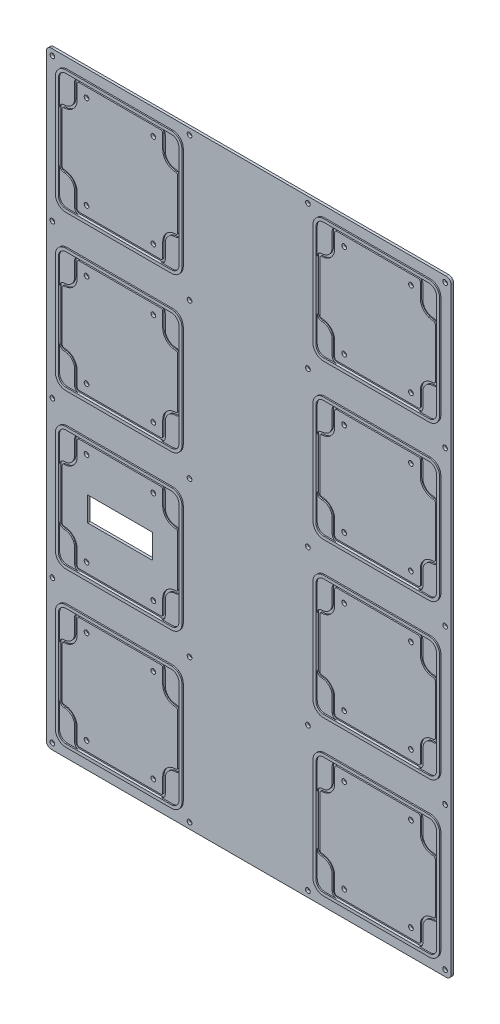
SolidWorks part; units mm, degrees
ref_plane "Front Plane" through (0, 0, 0) normal (0, 0, 1) x (1, 0, 0)
ref_plane "Top Plane" through (0, 0, 0) normal (0, 1, 0) x (1, 0, 0)
ref_plane "Right Plane" through (0, 0, 0) normal (1, 0, 0) x (0, 0, -1)
sketch "Sketch1" plane through (0, 0, 0) normal (0, 0, 1) x (1, 0, 0)
  line L1 (0, 0) -> (254, 0)
  line L2 (0, 0) -> (0, 381)
  line L3 (0, 381) -> (254, 381)
  line L4 (254, 0) -> (254, 381)
  dimension "D1" = 381
  dimension "D2" = 254
extrude "Boss-Extrude1" add sketch "Sketch1" along normal blind 1.5875
sketch "Sketch2" plane through (0, 0, 1.5875) normal (0, 0, 1) x (1, 0, 0)
  line L0 (89.8652, 377.19) -> (89.8652, 3.81) construction
  line L1 (0, 381) -> (254, 381) construction
  line L2 (127, 381) -> (127, 377.19) construction
  line L3 (3.81, 377.19) -> (250.19, 377.19) construction
  line L5 (164.1348, 377.19) -> (164.1348, 3.81) construction
  line L6 (3.81, 377.19) -> (3.81, 3.81) construction
  line L7 (3.81, 3.81) -> (250.19, 3.81) construction
  line L8 (250.19, 3.81) -> (250.19, 377.19) construction
  line L9 (3.81, 190.5) -> (250.19, 190.5) construction
  line L10 (3.81, 287.3756) -> (250.19, 287.3756) construction
  line L11 (3.81, 93.6244) -> (250.19, 93.6244) construction
  line L12 (0, 381) -> (0, 0) construction
  line L13 (0, 190.5) -> (3.81, 190.5) construction
  circle A0 centre (3.81, 377.19) radius 1.4732
  circle A1 centre (89.8652, 377.19) radius 1.4732
  circle A2 centre (164.1348, 377.19) radius 1.4732
  circle A3 centre (250.19, 377.19) radius 1.4732
  circle A4 centre (164.1348, 287.3755) radius 1.4732
  circle A5 centre (3.81, 287.3756) radius 1.4732
  circle A6 centre (250.19, 287.3756) radius 1.4732
  circle A7 centre (89.8652, 287.3756) radius 1.4732
  circle A8 centre (164.1348, 190.5) radius 1.4732
  circle A9 centre (3.81, 191.135) radius 1.4732
  circle A10 centre (250.19, 190.5) radius 1.4732
  circle A11 centre (89.8652, 190.5) radius 1.4732
  circle A12 centre (164.1348, 93.6244) radius 1.4732
  circle A13 centre (3.81, 93.6244) radius 1.4732
  circle A14 centre (250.19, 93.6244) radius 1.4732
  circle A15 centre (89.8652, 93.6244) radius 1.4732
  circle A16 centre (164.1348, 3.81) radius 1.4732
  circle A17 centre (3.81, 3.81) radius 1.4732
  circle A18 centre (250.19, 3.81) radius 1.4732
  circle A19 centre (89.8652, 3.81) radius 1.4732
  dimension "D6" = 2.9464
  dimension "D23" = 0
  dimension "D24" = 0
  dimension "D25" = 0
  dimension "D28" = 0
  dimension "D29" = 0
  dimension "D30" = 0
  dimension "D31" = 0
  dimension "D32" = 86.0552
  dimension "D1" = 246.38
  dimension "D3" = 373.38
  dimension "D4" = 96.8756
  dimension "D5" = 96.8756
  dimension "D7" = 86.0552
  dimension "D8" = 86.0552
  dimension "D9" = 0
  dimension "D10" = 0
  dimension "D11" = 0
  dimension "D12" = 86.0552
  dimension "D13" = 0
  dimension "D14" = 0
  dimension "D15" = 0
  dimension "D16" = 0
  dimension "D17" = 0
  dimension "D18" = 0
  dimension "D19" = 0
  dimension "D20" = 0
  dimension "D21" = 0
  dimension "D22" = 0
  dimension "D26" = 0
  dimension "D27" = 0
extrude "Cut-Extrude1" cut sketch "Sketch2" against normal through all
fillet "Fillet1" radius 3.175 4 edges at (254, 0, 0.7937) (0, 0, 0.7937) (254, 381, 0.7937) (0, 381, 0.7937)
sketch "Sketch3" plane through (0, 0, 1.5875) normal (0, 0, 1) x (1, 0, 0)
  line L0 (9.9695, 45.1866) -> (46.2026, 45.1866) construction
  line L1 (46.2026, 45.1866) -> (46.2026, 9.9695) construction
  line L2 (81.2038, 28.3591) -> (82.4357, 28.3591) construction
  line L3 (82.4357, 29.591) -> (82.4357, 60.7822)
  line L4 (73.0377, 11.2014) -> (73.0377, 20.193)
  line L5 (81.2038, 62.0141) -> (82.4357, 62.0141) construction
  line L6 (71.8058, 9.9695) -> (20.5994, 9.9695)
  line L7 (19.3675, 11.2014) -> (19.3675, 20.193)
  line L8 (11.2014, 28.3591) -> (9.9695, 28.3591) construction
  line L9 (9.9695, 29.591) -> (9.9695, 60.7822)
  line L10 (73.0377, 79.1718) -> (73.0377, 70.1802)
  line L11 (71.8058, 80.4037) -> (20.5994, 80.4037)
  line L12 (3.175, 0) -> (250.825, 0) construction
  line L13 (0, 377.825) -> (0, 3.175) construction
  line L14 (11.2014, 62.0141) -> (9.9695, 62.0141) construction
  line L15 (19.3675, 79.1718) -> (19.3675, 70.1802)
  line L16 (17.78, 79.1718) -> (17.78, 70.1802)
  line L17 (8.382, 29.591) -> (8.382, 60.7822)
  line L18 (17.78, 11.2014) -> (17.78, 20.193)
  line L19 (71.8058, 8.382) -> (20.5994, 8.382)
  line L20 (74.6252, 11.2014) -> (74.6252, 20.193)
  line L21 (84.0232, 29.591) -> (84.0232, 60.7822)
  line L22 (74.6252, 79.1718) -> (74.6252, 70.1802)
  line L23 (71.8058, 81.9912) -> (20.5994, 81.9912)
  arc A0 (19.3675, 20.193) -> (11.2014, 28.3591) centre (11.2014, 20.193) ccw
  arc A1 (9.9695, 29.591) -> (11.2014, 28.3591) centre (11.2014, 29.591) ccw
  arc A2 (19.3675, 11.2014) -> (20.5994, 9.9695) centre (20.5994, 11.2014) ccw
  arc A3 (73.0377, 11.2014) -> (71.8058, 9.9695) centre (71.8058, 11.2014) cw
  arc A4 (82.4357, 29.591) -> (81.2038, 28.3591) centre (81.2038, 29.591) cw
  arc A5 (73.0377, 20.193) -> (81.2038, 28.3591) centre (81.2038, 20.193) cw
  arc A6 (73.0377, 70.1802) -> (81.2038, 62.0141) centre (81.2038, 70.1802) ccw
  arc A7 (82.4357, 60.7822) -> (81.2038, 62.0141) centre (81.2038, 60.7822) ccw
  arc A8 (73.0377, 79.1718) -> (71.8058, 80.4037) centre (71.8058, 79.1718) ccw
  arc A9 (19.3675, 79.1718) -> (20.5994, 80.4037) centre (20.5994, 79.1718) cw
  arc A10 (9.9695, 60.7822) -> (11.2014, 62.0141) centre (11.2014, 60.7822) cw
  arc A11 (19.3675, 70.1802) -> (11.2014, 62.0141) centre (11.2014, 70.1802) cw
  arc A12 (17.78, 70.1802) -> (11.2014, 63.6016) centre (11.2014, 70.1802) cw
  arc A13 (8.382, 60.7822) -> (11.2014, 63.6016) centre (11.2014, 60.7822) cw
  arc A14 (8.382, 29.591) -> (11.2014, 26.7716) centre (11.2014, 29.591) ccw
  arc A15 (17.78, 20.193) -> (11.2014, 26.7716) centre (11.2014, 20.193) ccw
  arc A16 (17.78, 11.2014) -> (20.5994, 8.382) centre (20.5994, 11.2014) ccw
  arc A17 (74.6252, 11.2014) -> (71.8058, 8.382) centre (71.8058, 11.2014) cw
  arc A18 (74.6252, 20.193) -> (81.2038, 26.7716) centre (81.2038, 20.193) cw
  arc A19 (84.0232, 29.591) -> (81.2038, 26.7716) centre (81.2038, 29.591) cw
  arc A20 (84.0232, 60.7822) -> (81.2038, 63.6016) centre (81.2038, 60.7822) ccw
  arc A21 (74.6252, 70.1802) -> (81.2038, 63.6016) centre (81.2038, 70.1802) ccw
  arc A22 (74.6252, 79.1718) -> (71.8058, 81.9912) centre (71.8058, 79.1718) ccw
  arc A23 (17.78, 79.1718) -> (20.5994, 81.9912) centre (20.5994, 79.1718) cw
  point P35 (82.4357, 45.1866)
  dimension "D6" = 8.1661
  dimension "D7" = 2.4638
  dimension "D8" = 1.2319
  dimension "D1" = 9.9695
  dimension "D2" = 9.9695
  dimension "D3" = 19.3675
  dimension "D4" = 28.3591
  dimension "D5" = 45.1866
  dimension "D10" = 46.2026
  dimension "D9" = 1.5875
extrude "Cut-Extrude2" cut sketch "Sketch3" against normal blind 0.7937
sketch "Sketch4" plane through (0, 0, 1.5875) normal (0, 0, 1) x (1, 0, 0)
  line L0 (8.382, 60.7822) -> (8.382, 77.2287)
  line L1 (13.1445, 81.9912) -> (20.5994, 81.9912)
  line L2 (20.5994, 81.9912) -> (79.2607, 81.9912)
  line L3 (84.0232, 77.2287) -> (84.0232, 13.1445)
  line L4 (79.2607, 8.382) -> (13.1445, 8.382)
  line L5 (8.382, 13.1445) -> (8.382, 60.7822)
  line L6 (6.477, 60.7822) -> (6.477, 77.2287)
  line L7 (13.1445, 83.8962) -> (20.5994, 83.8962)
  line L8 (20.5994, 83.8962) -> (79.2607, 83.8962)
  line L9 (85.9282, 77.2287) -> (85.9282, 13.1445)
  line L10 (79.2607, 6.477) -> (13.1445, 6.477)
  line L11 (6.477, 13.1445) -> (6.477, 60.7822)
  arc A0 (13.1445, 81.9912) -> (8.382, 77.2287) centre (13.1445, 77.2287) ccw
  arc A1 (79.2607, 81.9912) -> (84.0232, 77.2287) centre (79.2607, 77.2287) cw
  arc A2 (84.0232, 13.1445) -> (79.2607, 8.382) centre (79.2607, 13.1445) cw
  arc A3 (8.382, 13.1445) -> (13.1445, 8.382) centre (13.1445, 13.1445) ccw
  arc A4 (13.1445, 83.8962) -> (6.477, 77.2287) centre (13.1445, 77.2287) ccw
  arc A5 (79.2607, 83.8962) -> (85.9282, 77.2287) centre (79.2607, 77.2287) cw
  arc A6 (85.9282, 13.1445) -> (79.2607, 6.477) centre (79.2607, 13.1445) cw
  arc A7 (6.477, 13.1445) -> (13.1445, 6.477) centre (13.1445, 13.1445) ccw
  dimension "D1" = 4.7625
  dimension "D2" = 1.905
extrude "Boss-Extrude2" add sketch "Sketch4" along normal blind 0.7937
sketch "Sketch5" plane through (0, 0, 1.5875) normal (0, 0, 1) x (1, 0, 0)
  line L0 (9.9695, 45.1866) -> (82.4357, 45.1866) construction
  line L1 (9.9695, 60.7822) -> (9.9695, 29.591) construction
  line L2 (82.4357, 29.591) -> (82.4357, 60.7822) construction
  line L3 (82.4357, 45.1866) -> (46.2026, 45.1866) construction
  line L4 (46.2026, 45.1866) -> (46.2026, 80.4037) construction
  line L5 (71.8058, 80.4037) -> (20.5994, 80.4037) construction
  circle A0 centre (25.2476, 74.3966) radius 1.4732
  circle A1 centre (67.1576, 74.3966) radius 1.4732
  circle A2 centre (67.1576, 15.9766) radius 1.4732
  circle A3 centre (25.2476, 15.9766) radius 1.4732
  dimension "D1" = 2.9464
  dimension "D2" = 20.955
  dimension "D3" = 29.21
extrude "Cut-Extrude3" cut sketch "Sketch5" against normal through all
pattern_linear "LPattern1" count 4 spacing 96.8756 along (0, 1, 0) count 2 spacing 161.5948 along (1, 0, 0) of "Cut-Extrude2", "Boss-Extrude2", "Cut-Extrude3"
sketch "Sketch6" plane through (0, 0, 1.5875) normal (0, 0, 1) x (1, 0, 0)
  line L0 (25.8826, 142.0622) -> (9.9695, 142.0622) construction
  line L1 (25.8826, 149.6822) -> (66.5226, 149.6822)
  line L2 (25.8826, 149.6822) -> (25.8826, 134.4422)
  line L3 (25.8826, 134.4422) -> (66.5226, 134.4422)
  line L4 (66.5226, 149.6822) -> (66.5226, 134.4422)
  line L5 (9.9695, 157.6578) -> (9.9695, 126.4666) construction
  line L6 (66.5226, 142.0622) -> (82.4357, 142.0622) construction
  line L7 (82.4357, 126.4666) -> (82.4357, 157.6578) construction
  line L8 (46.2026, 149.6822) -> (46.2026, 177.2793) construction
  line L9 (71.8058, 177.2793) -> (20.5994, 177.2793) construction
  line L10 (46.2026, 134.4422) -> (46.2026, 106.8451) construction
  line L11 (20.5994, 106.8451) -> (71.8058, 106.8451) construction
  dimension "D1" = 15.24
  dimension "D2" = 40.64
extrude "Cut-Extrude4" cut sketch "Sketch6" against normal through all
